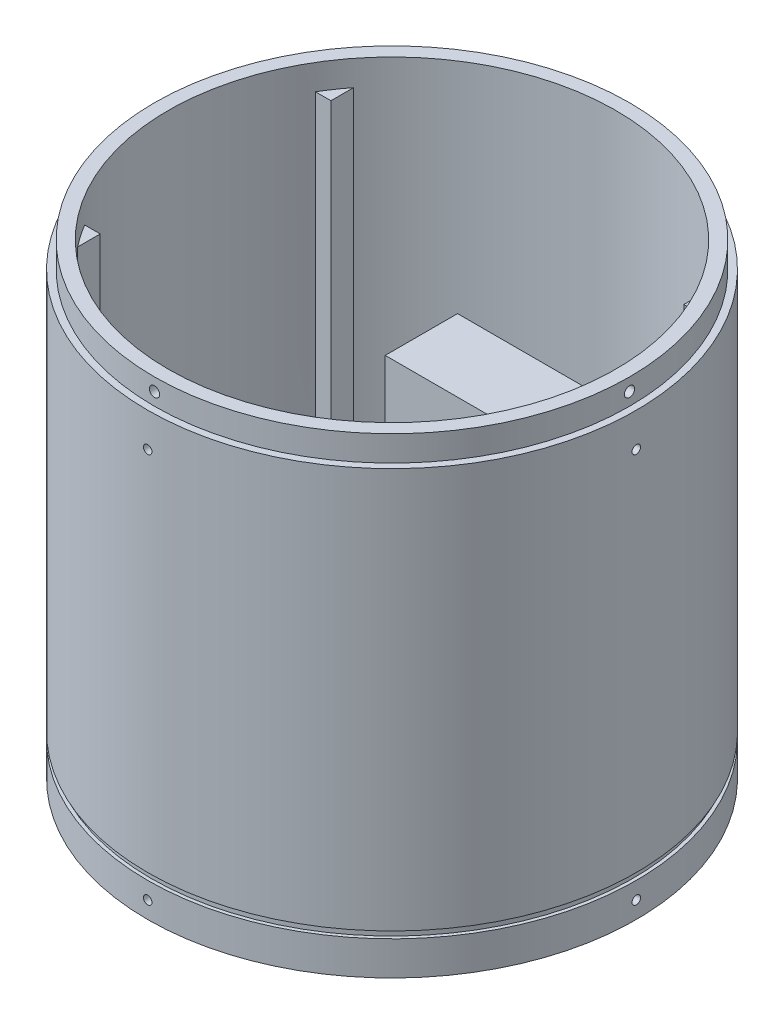
SolidWorks part; units mm, degrees
ref_plane "前基準面" through (0, 0, 0) normal (0, 0, 1) x (1, 0, 0)
ref_plane "上基準面" through (0, 0, 0) normal (0, 1, 0) x (1, 0, 0)
ref_plane "右基準面" through (0, 0, 0) normal (1, 0, 0) x (0, 0, -1)
sketch "草圖6" plane through (0, 0, 0) normal (0, 1, 0) x (1, 0, 0)
  line L0 (0, 0) -> (-95.9878, 0) construction
  line L1 (0, 0) -> (-70, 0) construction
  circle A0 centre (0, 0) radius 66
  circle A1 centre (0, 0) radius 70
  circle A2 centre (0, 0) radius 72
  point P5 (-70, 0)
  point P10 (0, 70)
  point P11 (70, 0)
  point P12 (0, -70)
  dimension "D1" = 2
  dimension "D2" = 4
  dimension "D3" = 144
  dimension "D4" = 4
  dimension "D5" = 70
sketch "草圖7" plane through (0, 0, 0) normal (0, 1, 0) x (1, 0, 0)
  line L1 (-34, 34) -> (34, 34)
  line L2 (-34, 34) -> (-34, -34)
  line L3 (-34, -34) -> (34, -34)
  line L4 (34, 34) -> (34, -34)
  line L5 (-34, 34) -> (34, -34) construction
  line L6 (-34, -34) -> (34, 34) construction
  point P0 (0, 0)
  point P7 (-30, 30)
  point P10 (30, 30)
  point P11 (30, -30)
  point P12 (-30, -30)
  point P13 (0, 0)
  dimension "D1" = 68
  dimension "D2" = 4
  dimension "D3" = 4
extrude "填料-伸長1" add sketch "草圖6" along normal blind 130 contours A2 A1 region at (-71.7964, 0, 0)
extrude "填料-伸長2" add sketch "草圖6<15>" along normal blind 137.5 contours A1 A0 region at (-68.0201, 0, 0)
sketch "草圖6<15>" plane through (0, 0, 0) normal (0, 1, 0) x (1, 0, 0) same geometry as "草圖6"
extrude "填料-伸長3" add sketch "草圖6<16>" along normal blind 3 contours A0 region at (0, 0, 0)
sketch "草圖6<16>" plane through (0, 0, 0) normal (0, 1, 0) x (1, 0, 0) same geometry as "草圖6"
sketch "草圖9" plane through (0, 0, 0) normal (0, 1, 0) x (1, 0, 0)
  line L0 (0, 0) -> (0, 39.247) construction
  line L1 (52, 67.0867) -> (52, -71.5265)
  line L2 (-96.5637, -34) -> (97.4044, -34)
  line L4 (-52, 67.0867) -> (-52, -71.5265)
  line L5 (-56.5685, 34) -> (88.304, 34)
  circle A0 centre (0, 0) radius 66
  circle A1 centre (0, 0) radius 70
  circle A2 centre (0, 0) radius 72
  dimension "D1" = 2
  dimension "D2" = 4
  dimension "D3" = 144
  dimension "D4" = 52
extrude "填料-伸長6" add sketch "草圖9" along normal up to surface (130 mm away) contours L4 A0 L5 | L2 A0 L4 | L1 A0 L2 | L5 A0 L1 region at (53.5564, 0, -36.2624) region at (-53.5564, 0, -36.2624) region at (53.5564, 0, 36.2624) region at (-53.5564, 0, 36.2624) up to face at (0, 130, 70)
sketch "草圖30" plane through (0, 0, 0) normal (1, 0, 0) x (0, 0, -1)
  line L0 (0, 137.5) -> (0, 130) construction
  line L1 (70, 137.5) -> (-70, 137.5) construction
  line L2 (72, 130) -> (-72, 130) construction
  point P6 (0, 133.75)
  dimension "D1" = 3.75
hole_wizard "Ø2.5mm 定位孔3" positions "3D草圖17" profile "草圖31" hole size "Ø3.0" standard "JIS"
sketch3d "3D草圖17"
  point P0 (70, 133.75, 0)
  point P17 (70, 133.75, 0)
  point P19 (70, 133.75, 0)
sketch "草圖31" plane through (70, 133.75, 0) normal (0, 1, 0) x (0, 0, -1)
  line L0 (0, 0) -> (0, 3.9013)
  line L1 (0, 3.9013) -> (1.5, 3)
  line L2 (1.5, 3) -> (1.5, 0)
  line L5 (1.5, 0) -> (0, 0)
  line L10 (0, 3.9013) -> (-1.5, 3) construction
  line L11 (0, -6.35) -> (0, 107.95) construction
  dimension "鑽孔直徑" = 3
  dimension "鑽孔深度" = 3
  dimension "導頭角度" = 118
pattern_circular "環狀複製排列1" count 4 over 360 about axis through (0, 137.5, 0) along (0, 1, 0) of "Ø2.5mm 定位孔3"
ref_plane "平面4" through (0, 0, 0) normal (0, 0, 1) x (1, 0, 0)
sketch "草圖33" plane through (0, 0, 0) normal (0, 0, 1) x (1, 0, 0)
  line L5 (-72, 12) -> (-71, 12)
  line L6 (-71, 12) -> (-71, 10)
  line L7 (-71, 10) -> (-72, 10)
  line L9 (72, 0) -> (-72, 0) construction
  line L10 (-72, 12) -> (-72, 10)
  line L11 (-72, 130) -> (-72, 0) construction
  dimension "D1" = 1
  dimension "D2" = 2
  dimension "D6" = 10
revolve "除料-旋轉1" cut sketch "草圖33" angle 360 about L0
sketch "草圖35" plane through (0, 0, 0) normal (0, 0, 1) x (1, 0, 0)
  line L0 (-72, 10) -> (-72, 0) construction
  point P0 (-72, 5)
hole_wizard "M3x0.5  螺絲攻的螺孔鑽1" positions "3D草圖20" profile "草圖37" hole size "M3x0.5" standard "JIS"
sketch3d "3D草圖20"
  point P0 (-72, 5, 0)
sketch "草圖37" plane through (-72, 5, 0) normal (0, 1, 0) x (0, 0, 1)
  line L0 (0, 0) -> (0, 4.7511)
  line L1 (0, 4.7511) -> (1.25, 4)
  line L2 (1.25, 4) -> (1.25, 0)
  line L5 (1.25, 0) -> (0, 0)
  line L10 (0, 4.7511) -> (-1.25, 4) construction
  line L11 (0, -6.35) -> (0, 107.95) construction
  dimension "鑽孔直徑" = 2.5
  dimension "鑽孔深度" = 4
  dimension "導頭角度" = 118
pattern_circular "環狀複製排列2" count 4 over 360 about axis through (0, 137.5, 0) along (0, -1, 0) of "M3x0.5  螺絲攻的螺孔鑽1"
sketch "草圖39" plane through (0, 0, 0) normal (0, 1, 0) x (1, 0, 0)
  line L0 (-56.5685, 34) -> (56.5685, 34)
  line L2 (-56.5685, -34) -> (56.5685, -34)
  line L5 (0, 0) -> (0, 19.0172) construction
  line L6 (0, 0) -> (-12.2861, 0) construction
  line L7 (-56.707, 13) -> (-56.707, -13)
  line L8 (-64.707, 13) -> (64.707, 13)
  line L9 (56.707, 13) -> (56.707, -13)
  line L10 (-64.707, -13) -> (64.7924, -12.5675)
  arc A0 (-64.707, -13) -> (-56.5685, -34) centre (0, 0) ccw
  arc A3 (-56.5685, 34) -> (-64.707, 13) centre (0, 0) ccw
  arc A4 (64.707, 13) -> (56.5685, 34) centre (0, 0) ccw
  arc A5 (56.5685, -34) -> (64.7924, -12.5675) centre (0, 0) ccw
  point P12 (-49, 22)
  point P24 (56.707, 0)
  point P27 (-56.707, 0)
  dimension "D1" = 8
  dimension "D2" = 13
  dimension "D5" = 12
sketch "草圖40" plane through (0, 3, 0) normal (0, 1, 0) x (1, 0, 0)
  line L0 (-34, 34) -> (34, 34) construction
  line L1 (-36, 55.3173) -> (36, 55.3173)
  line L2 (-36, 55.3173) -> (-36, 34)
  line L3 (-36, 34) -> (36, 34)
  line L4 (36, 55.3173) -> (36, 34)
  line L5 (-36, 55.3173) -> (36, 34) construction
  line L6 (-36, 34) -> (36, 55.3173) construction
  circle A1 centre (0, 0) radius 66 construction
  point P0 (0, 44.6586)
  dimension "D1" = 21.3173
  dimension "D2" = 72
sketch "草圖41" plane through (0, 3, 0) normal (0, 1, 0) x (1, 0, 0)
  line L0 (0, 0) -> (-95.9878, 0) construction
  line L1 (-63.7154, 5.5) -> (56.2846, 5.5)
  line L2 (-63.7154, 5.5) -> (-63.7154, -5.5)
  line L3 (-63.7154, -5.5) -> (56.2846, -5.5)
  line L4 (56.2846, 5.5) -> (56.2846, -5.5)
  line L5 (-63.7154, 5.5) -> (56.2846, -5.5) construction
  line L6 (-63.7154, -5.5) -> (56.2846, 5.5) construction
  point P0 (-3.7154, 0)
  dimension "D1" = 11
  dimension "D2" = 120
extrude "填料-伸長8" add sketch "草圖40" along normal blind 70 separate body
pattern_linear "直線複製排列2" count 2 spacing 115 along (0, 1, 0) of "環狀複製排列2"
